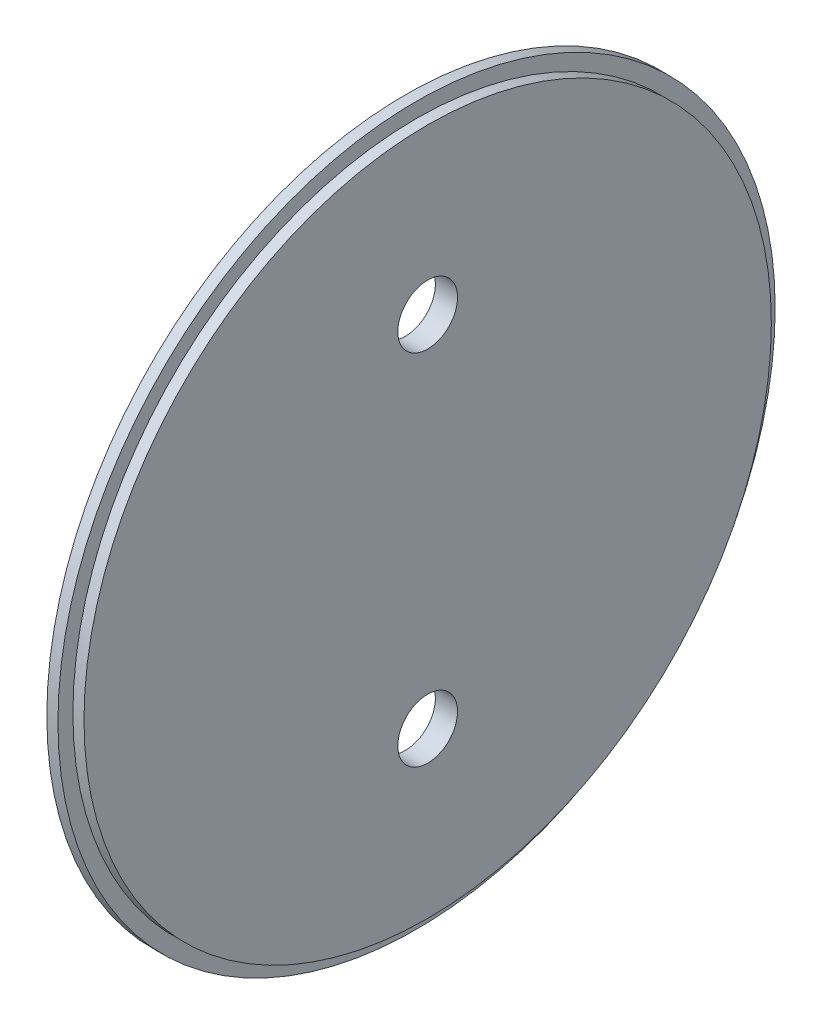
SolidWorks part; units mm, degrees
ref_plane "Front Plane" through (0, 0, 0) normal (1, 0, 0) x (0, 1, 0)
ref_plane "Top Plane" through (0, 0, 0) normal (0, 0, 1) x (0, 1, 0)
ref_plane "Right Plane" through (0, 0, 0) normal (0, 1, 0) x (-1, 0, 0)
sketch "Sketch1" plane through (0, 0, 0) normal (1, 0, 0) x (0, 1, 0)
  circle A0 centre (0, 0) radius 38.1
  dimension "D1" = 76.2
extrude "Boss-Extrude1" add sketch "Sketch1" along normal blind 1.1811
sketch "Sketch2" plane through (1.1811, 0, 0) normal (1, 0, 0) x (0, 1, 0)
  circle A0 centre (0, 0) radius 36.5125
  dimension "D1" = 73.025
extrude "Boss-Extrude2" add sketch "Sketch2" along normal blind 1.1811
sketch "Sketch3" plane through (0, 0, 0) normal (-1, 0, 0) x (0, -1, 0)
  circle A1 centre (19.05, 0) radius 3.175
  circle A2 centre (-19.05, 0) radius 3.175
  point P0 (0, 0)
  point P7 (0, 0)
  dimension "D1" = 19.05
  dimension "D2" = 6.35
  dimension "D3" = 6.35
  dimension "D4" = 19.05
extrude "Cut-Extrude1" cut sketch "Sketch3" against normal through all
